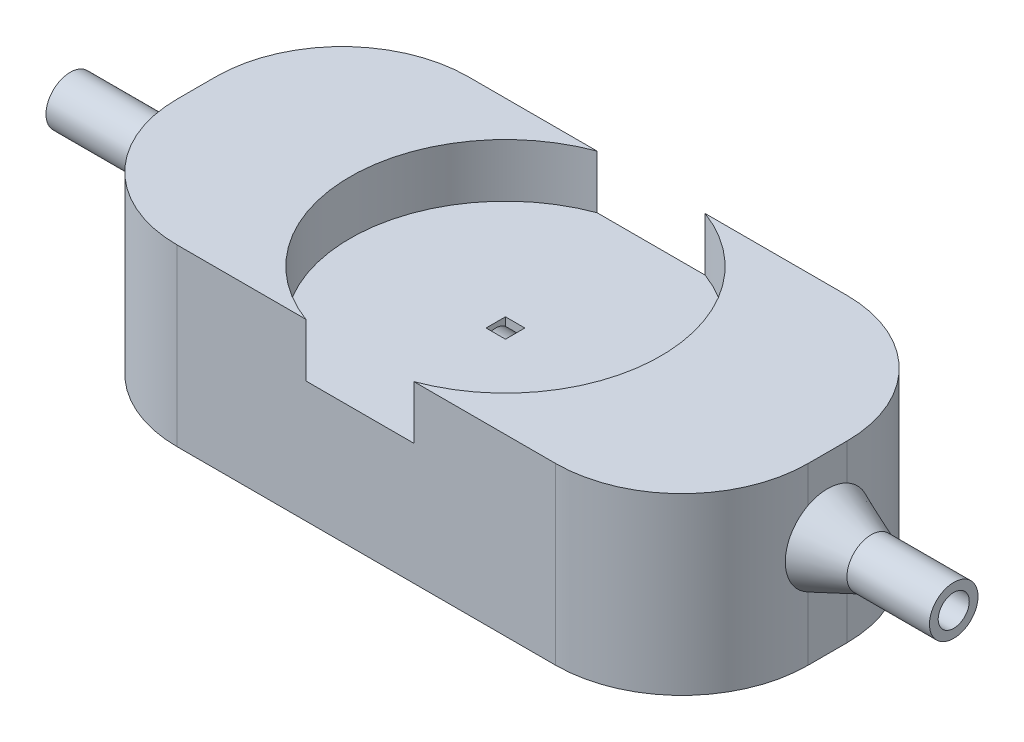
SolidWorks part; units mm, degrees
ref_plane "Front Plane" through (0, 0, 0) normal (0, 0, 1) x (1, 0, 0)
ref_plane "Top Plane" through (0, 0, 0) normal (0, 1, 0) x (1, 0, 0)
ref_plane "Right Plane" through (0, 0, 0) normal (1, 0, 0) x (0, 0, -1)
sketch "Sketch1" plane through (0, 0, 0) normal (0, 1, 0) x (1, 0, 0)
  line L1 (-25, -15) -> (40, -15)
  line L2 (-25, -15) -> (-25, 15)
  line L3 (-25, 15) -> (40, 15)
  line L4 (40, -15) -> (40, 15)
  line L5 (-25, -15) -> (40, 15) construction
  line L6 (-25, 15) -> (40, -15) construction
  point P0 (0, 0)
  dimension "D1" = 30
  dimension "D2" = 65
extrude "Boss-Extrude1" add sketch "Sketch1" along normal blind 58
sketch "Sketch3" plane through (-25, 0, 0) normal (-1, 0, 0) x (0, 0, 1)
  line L0 (-15, 58) -> (15, 58) construction
  circle A0 centre (0, 50.4) radius 1.6
  dimension "D1" = 3.2
  dimension "D2" = 7.6
fillet "Fillet1" radius 13 4 edges at (40, 29, -15) (-25, 29, -15) (40, 29, 15) (-25, 29, 15)
ref_plane "Plane2" through (0, -10, 0) normal (0, -1, 0) x (-1, 0, 0)
sketch "Sketch15" plane through (0, -10, 0) normal (0, -1, 0) x (-1, 0, 0)
  line L1 (-41.9055, 15.8797) -> (41.7906, 15.8797)
  line L2 (-41.9055, 15.8797) -> (-41.9055, -15.8187)
  line L3 (-41.9055, -15.8187) -> (41.7906, -15.8187)
  line L4 (41.7906, 15.8797) -> (41.7906, -15.8187)
extrude "Cut-Extrude7" cut sketch "Sketch15" against normal blind 50
ref_plane "Plane3" through (0, 40, 0) normal (0, -1, 0) x (-1, 0, 0)
ref_plane "Plane4" through (0, 58, 0) normal (0, 1, 0) x (1, 0, 0)
sketch "Sketch18" plane through (0, 58, 0) normal (0, 1, 0) x (1, 0, 0)
  circle A0 centre (6.8285, 0) radius 16
  dimension "D1" = 32
extrude "Cut-Extrude10" cut sketch "Sketch18" against normal blind 5.5
extrude "Cut-Extrude12" cut sketch "Sketch3" against normal up to next
ref_plane "Plane5" through (0, 52.5, 0) normal (0, 1, 0) x (1, 0, 0)
sketch "Sketch21" plane through (0, 52.5, 0) normal (0, 1, 0) x (1, 0, 0)
  line L1 (5.8285, -1) -> (7.8285, -1)
  line L2 (5.8285, -1) -> (5.8285, 1)
  line L3 (5.8285, 1) -> (7.8285, 1)
  line L4 (7.8285, -1) -> (7.8285, 1)
  line L5 (5.8285, -1) -> (7.8285, 1) construction
  line L6 (5.8285, 1) -> (7.8285, -1) construction
  point P0 (6.8285, 0)
  dimension "D1" = 2
  dimension "D2" = 2
extrude "Cut-Extrude13" cut sketch "Sketch21" against normal blind 8
ref_plane "Plane7" through (-25, 0, 0) normal (-1, 0, 0) x (0, 0, 1)
sketch "Sketch24" plane through (0, 0, 0) normal (0, 0, 1) x (1, 0, 0)
  line L1 (-25, 52) -> (-25, 48.8) construction
  line L5 (-25, 50.4) -> (-31.2466, 50.4) construction
  line L7 (-25, 50.4) -> (46.09, 50.4) construction
  line L8 (-25, 52) -> (-38, 52)
  line L9 (-29.5, 52.9) -> (-38, 52.9)
  line L10 (-38, 52.9) -> (-38, 52)
  line L11 (-25, 40) -> (-25, 58) construction
  line L12 (-29.5, 52.9) -> (-25, 54.7499)
  line L13 (-25, 52) -> (-25, 54.7499)
  point P1 (-25, 55.5175)
  point P4 (-25, 54.4012)
  point P9 (-25, 54.7499)
  dimension "D1" = 1.6
  dimension "D2" = 8.6998
  dimension "D3" = 2.5
  dimension "D4" = 13
  dimension "D5" = 4.5
revolve "Revolve1" add sketch "Sketch24" angle 360 about L5
sketch "Sketch25" plane through (0, 0, 0) normal (0, 0, 1) x (1, 0, 0)
  line L1 (50.4822, 50.3986) -> (44.2356, 50.3986) construction
  line L13 (40, 51.9986) -> (40, 54.7486)
  line L14 (40, 58) -> (40, 40) construction
  line L15 (40, 54.7486) -> (44.5, 52.8986)
  line L16 (44.5, 52.8986) -> (53, 52.8986)
  line L17 (53, 52.8986) -> (53, 51.9986)
  line L18 (53, 51.9986) -> (40, 51.9986)
  dimension "D1" = 1.6
  dimension "D2" = 2.5
  dimension "D3" = 13
  dimension "D4" = 8.7
  dimension "D5" = 4.5
revolve "Revolve2" add sketch "Sketch25" angle 360 about L1
